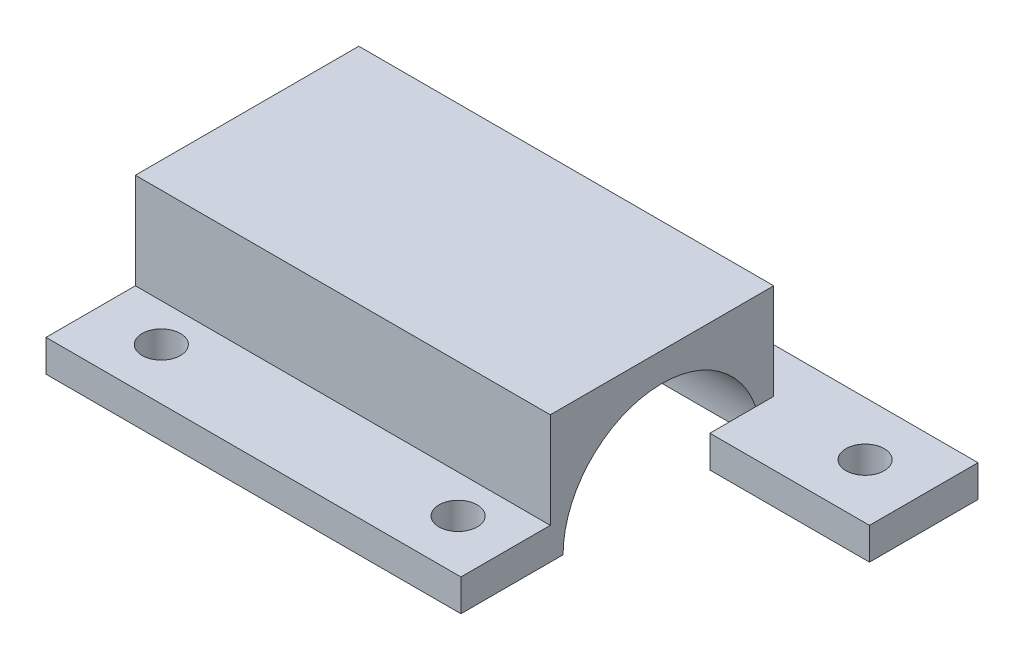
SolidWorks part; units mm, degrees
ref_plane "前视基准面" through (0, 0, 0) normal (0, 0, 1) x (1, 0, 0)
ref_plane "上视基准面" through (0, 0, 0) normal (0, 1, 0) x (1, 0, 0)
ref_plane "右视基准面" through (0, 0, 0) normal (1, 0, 0) x (0, 0, -1)
other "Configuration Table"
sketch "草图1" plane through (0, 0, 0) normal (1, 0, 0) x (0, 0, -1)
  line L0 (-6.3, 0) -> (6.3, 0)
  line L9 (-6.3, 0) -> (-6.3, 4)
  line L14 (-6.3, 4) -> (6.3, 4)
  line L15 (6.3, 4) -> (6.3, 0)
  line L16 (-3.5, 4) -> (-3.5, 0)
  line L17 (3.5, 4) -> (3.5, 0)
  line L18 (-6.3, 1) -> (-3.5, 1)
  line L19 (3.5, 1) -> (6.3, 1)
  line L20 (4.9, 1) -> (4.9, 0)
  circle A0 centre (0, 0) radius 3.1
  circle A2 centre (0, 0) radius 1.5
  dimension "D1" = 6.2
  dimension "D2" = 2.8
  dimension "D7" = 3
  dimension "D3" = 4
  dimension "D4" = 3.5
  dimension "D5" = 3.5
  dimension "D6" = 1
  dimension "D8" = 1.4
extrude "凸台-拉伸1" add sketch "草图1" against normal blind 18 contours L9 L16 L18 | L17 L15 L19 | A0 L17 L14 L16 region at (0, 0.5, 4.9) region at (0, 0.5, 3.4194) region at (0, 0.5, -4.2)
sketch "草图2" plane through (0, 1, 0) normal (0, 1, 0) x (1, 0, 0)
  circle A2 centre (-16, -4.6875) radius 0.6
  circle A3 centre (-6.7, -4.6875) radius 0.6
  point P4 (0, 0)
  point P7 (-16, -4.6875)
  point P9 (0, 0)
  point P10 (-6.4485, -4.6875)
  point P11 (-6.7741, -4.6875)
  point P12 (-6.7, -4.6875)
  point P14 (0, 0)
  dimension "D1" = 1.2
extrude "切除-拉伸1" cut sketch "草图2" against normal through all contours A2 | A3
sketch "草图3" plane through (0, 0, 0) normal (1, 0, 0) x (0, 0, -1)
  line L1 (-3.5, 4) -> (3.5, 4)
  line L2 (-3.5, 4) -> (-3.5, 1)
  line L3 (-3.5, 1) -> (3.5, 1)
  line L4 (3.5, 4) -> (3.5, 1)
extrude "切除-拉伸2" cut sketch "草图3" against normal blind 5
sketch "草图4" plane through (0, 1, 0) normal (0, 1, 0) x (1, 0, 0)
  line L0 (-5, 3.5) -> (-5, -3.5) construction
  line L1 (0, 4.9) -> (-5, 4.9)
  line L2 (0, 4.9) -> (0, 1.5)
  line L3 (0, 1.5) -> (-5, 1.5)
  line L4 (-5, 4.9) -> (-5, 1.5)
  dimension "D1" = 3.4
extrude "凸台-拉伸2" add sketch "草图4" against normal up to surface (1 mm away) up to face at (-9, 0, -4)
sketch "草图5" plane through (0, 1, 0) normal (0, 1, 0) x (1, 0, 0)
  circle A0 centre (-1.85, 3.2125) radius 0.6
  point P2 (-1.85, 3.2125)
  point P4 (0, 0)
  dimension "D1" = 1.2
extrude "切除-拉伸3" cut sketch "草图5" against normal through all
sketch "草图7" plane through (0, 0, 0) normal (1, 0, 0) x (0, 0, -1)
  line L1 (-2.9343, 1) -> (-6.3, 1)
  line L2 (-2.9343, 1) -> (-2.9343, 0)
  line L3 (-2.9343, 0) -> (-6.3, 0)
  line L4 (-6.3, 1) -> (-6.3, 0)
extrude "切除-拉伸4" cut sketch "草图7" against normal up to surface (5 mm away) up to face at (-5, 2.35, 0)
